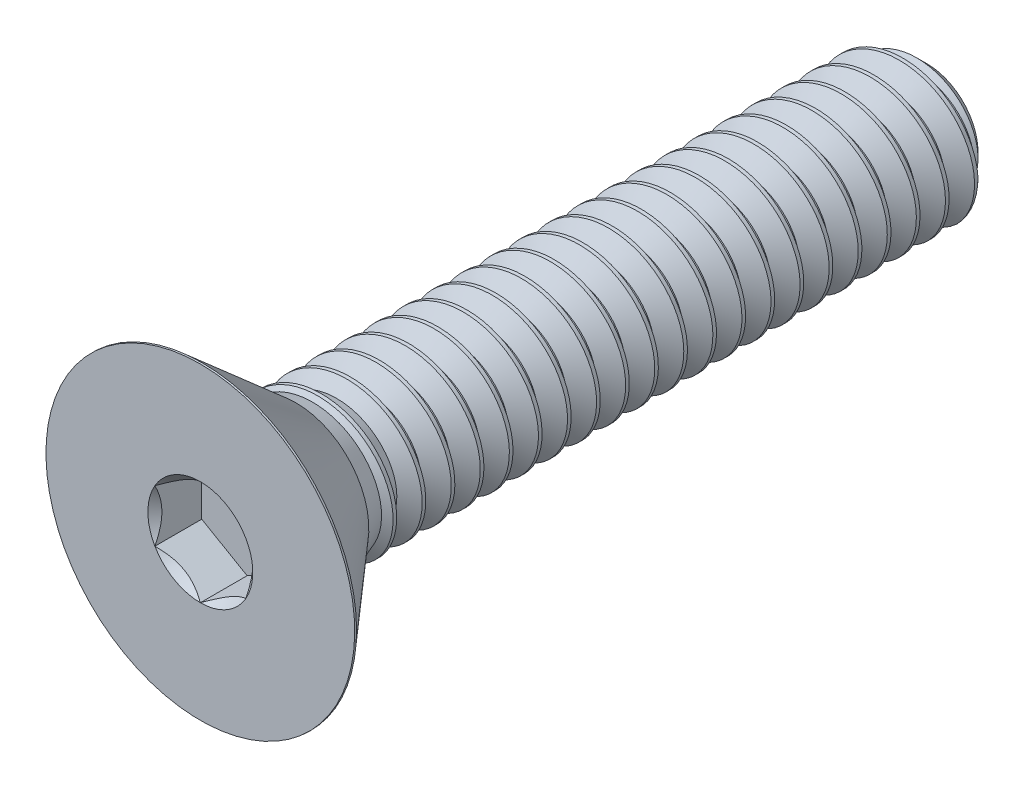
SolidWorks part; units mm, degrees
ref_plane "Front Plane" through (0, 0, 0) normal (0, 0, 1) x (1, 0, 0)
ref_plane "Top Plane" through (0, 0, 0) normal (0, 1, 0) x (1, 0, 0)
ref_plane "Right Plane" through (0, 0, 0) normal (1, 0, 0) x (0, 0, -1)
sketch "Sketch1" plane through (0, 0, 0) normal (1, 0, 0) x (0, 0, -1)
  line L0 (-15.875, 0) -> (15.875, 0) construction
  line L1 (-15.875, 0) -> (-15.875, 6.7437)
  line L2 (-15.875, 6.7437) -> (-15.7932, 6.7437)
  line L3 (-15.7932, 6.7437) -> (-11.7856, 3.2599)
  line L4 (-15.7932, -6.7437) -> (-11.7856, -3.2599)
  line L5 (15.875, 0) -> (15.875, 3.175)
  line L6 (15.875, 3.175) -> (-11.7856, 3.175)
  line L7 (14.9225, 3.175) -> (15.875, 2.2225)
  line L8 (15.7956, 3.3125) -> (16.4306, 2.2126) construction
  line L9 (16.4306, 2.2126) -> (17.0656, 3.3125) construction
  line L10 (17.0656, 3.3125) -> (15.7956, 3.3125) construction
  line L11 (15.8353, 3.2437) -> (17.0259, 3.2437)
  line L12 (17.0259, 3.2437) -> (16.51, 2.3501)
  line L13 (16.51, 2.3501) -> (16.3512, 2.3501)
  line L14 (16.3512, 2.3501) -> (15.8353, 3.2437)
  line L15 (16.4306, 2.3501) -> (16.4306, 2.2126) construction
  line L16 (15.875, 3.175) -> (16.9862, 3.175) construction
  line L17 (16.4306, 3.3125) -> (16.4306, 3.175) construction
  line L18 (15.875, -3.175) -> (-11.7856, -3.175)
  arc A0 (-11.7856, 3.2599) -> (-11.5584, 3.175) centre (-11.5584, 3.5213) ccw
  point P2 (0, 0)
  point P23 (-13.8303, 0)
  point P27 (16.4306, 3.2437)
  point P30 (13.97, -3.175)
  point P31 (-11.7856, 6.7437)
  point P33 (-11.7856, -6.7437)
  point P34 (-15.7932, -6.7437)
  dimension "Length" = 31.75
  dimension "Head Height" = 4.0894
  dimension "Head Diameter" = 13.4874
  dimension "Countersink Angle" = 82
  dimension "Screw Size Decimal Equivalent" = 6.35
  dimension "Pitch" = 1.27
  dimension "D4" = 0.1588
  dimension "D3" = 45
  dimension "D5" = 0.9525
  dimension "D6" = 2.0447
  dimension "D1" = 1.905
  dimension "D7" = 0.0818
sketch "Sketch8" plane through (0, 0, 0) normal (0, 0, 1) x (1, 0, 0)
  line L1 (0, 2.2914) -> (-1.9844, 1.1457)
  line L2 (-1.9844, 1.1457) -> (-1.9844, -1.1457)
  line L3 (-1.9844, -1.1457) -> (0, -2.2914)
  line L4 (0, -2.2914) -> (1.9844, -1.1457)
  line L5 (1.9844, -1.1457) -> (1.9844, 1.1457)
  line L6 (1.9844, 1.1457) -> (0, 2.2914)
  circle A0 centre (0, 0) radius 1.9844 construction
  dimension "Drive Size" = 3.9688
sketch "Sketch2" plane through (0, 0, 0) normal (1, 0, 0) x (0, 0, -1)
  line L0 (-15.7932, 6.7437) -> (-11.7856, 3.2599) construction
  line L1 (-15.875, 0) -> (-15.875, 6.7437) construction
  line L2 (-15.7932, 6.7437) -> (-11.6879, 3.175)
  line L3 (-15.875, 0) -> (-15.875, 6.7437)
  line L4 (-15.875, 6.7437) -> (-15.7932, 6.7437) construction
  line L5 (-15.875, 6.7437) -> (-15.7932, 6.7437)
  line L6 (-11.6879, 3.175) -> (14.9225, 3.175)
  line L7 (14.9225, 3.175) -> (15.875, 2.2225)
  line L8 (15.875, 2.2225) -> (15.875, 0)
  line L9 (15.875, 0) -> (-15.875, 0)
revolve "Revolve1" add sketch "Sketch2" angle 360 about L9
sketch "Sketch9" plane through (0, 0, 15.875) normal (0, 0, 1) x (1, 0, 0)
  line L0 (1.9844, -1.1457) -> (1.9844, 1.1457) construction
  line L1 (0, -2.2914) -> (1.9844, -1.1457) construction
  line L2 (-1.9844, -1.1457) -> (0, -2.2914) construction
  line L3 (-1.9844, 1.1457) -> (-1.9844, -1.1457) construction
  line L4 (0, 2.2914) -> (-1.9844, 1.1457) construction
  line L5 (1.9844, 1.1457) -> (0, 2.2914) construction
  line L6 (1.9844, -1.1457) -> (1.9844, 1.1457)
  line L7 (0, -2.2914) -> (1.9844, -1.1457)
  line L8 (-1.9844, -1.1457) -> (0, -2.2914)
  line L9 (-1.9844, 1.1457) -> (-1.9844, -1.1457)
  line L10 (0, 2.2914) -> (-1.9844, 1.1457)
  line L11 (1.9844, 1.1457) -> (0, 2.2914)
sketch "Sketch10" plane through (0, 0, 15.875) normal (0, 0, 1) x (1, 0, 0)
  circle A0 centre (0, 0) radius 2.2914
extrude "Cut-Extrude2" cut sketch "Sketch10" against normal up to vertex (2.0447 mm away) draft 45 up to point (0, 0, 13.8303)
extrude "Cut-Extrude1" cut sketch "Sketch9" against normal up to vertex (2.0447 mm away) up to point (0, 0, 13.8303)
ref_plane "Plane1" through (0, 0, 11.6879) normal (0, 0, 1) x (1, 0, 0)
split "Split1" trim tools "Plane1" bodies to split 111 resulting bodies 105 106
sketch "Sketch3" plane through (0, 0, -15.875) normal (0, 0, -1) x (-1, 0, 0)
  circle A0 centre (0, 0) radius 3.175 construction
  circle A1 centre (0, 0) radius 3.175
curve "Helix/Spiral1" pitch 1.27 height 31.75 radius 3.175 centre (0, 0, -15.875) axis (0, 0, 1) start towards (0, 1, 0)
sketch "Sketch4" plane through (0, 0, 0) normal (1, 0, 0) x (0, 0, -1)
  line L0 (15.8353, 3.2437) -> (17.0259, 3.2437) construction
  line L1 (16.3512, 2.3501) -> (15.8353, 3.2437) construction
  line L2 (16.51, 2.3501) -> (16.3512, 2.3501) construction
  line L3 (17.0259, 3.2437) -> (16.51, 2.3501) construction
  line L4 (15.8353, 3.2437) -> (17.0259, 3.2437)
  line L5 (16.3512, 2.3501) -> (15.8353, 3.2437)
  line L6 (16.51, 2.3501) -> (16.3512, 2.3501)
  line L7 (17.0259, 3.2437) -> (16.51, 2.3501)
sweep "Cut-Sweep1" cut profiles "Sketch4" path "Helix/Spiral1" align with end faces yes
sketch "Sketch7" plane through (0, 0, 11.6879) normal (0, 0, 1) x (1, 0, 0)
  circle A0 centre (0, 0) radius 3.175
extrude "Boss-Extrude2" add sketch "Sketch7" against normal up to next (27.5629 mm away) draft 20
equation "\"D4@Sketch1\" = \"Pitch@Sketch1\" / 8"
equation "\"D5@Sketch1\"=\"Pitch@Sketch1\"*0.75"
equation "\"D4@Helix/Spiral1\"=\"Pitch@Sketch1\""
equation "\"D3@Helix/Spiral1\"=\"Length@Sketch1\""
equation "\"D6@Sketch1\"=\"Head Height@Sketch1\"/2"
equation "\"D1@Sketch1\"=\"Pitch@Sketch1\"*1.5"
equation "\"D7@Sketch1\"=\"Head Height@Sketch1\"*0.02"
